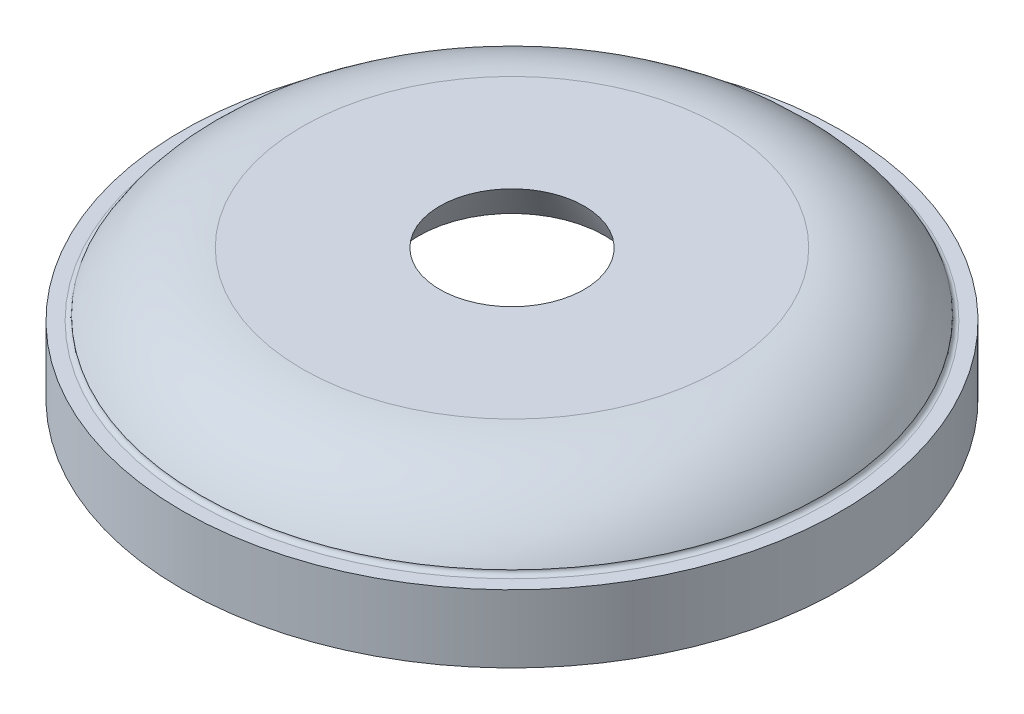
SolidWorks part; units mm, degrees
material "Silica Phenolic"
ref_plane "Piano frontale" through (0, 0, 0) normal (0, 0, 1) x (1, 0, 0)
ref_plane "Piano superiore" through (0, 0, 0) normal (0, 1, 0) x (1, 0, 0)
ref_plane "Piano destro" through (0, 0, 0) normal (1, 0, 0) x (0, 0, -1)
sketch "Schizzo1" plane through (0, 0, 0) normal (0, 0, 1) x (1, 0, 0)
  line L0 (-69, 0) -> (-73, 0)
  line L1 (-73, 0) -> (-73, 15)
  line L4 (-46.4833, 21) -> (-20.6188, 21)
  line L5 (-20.6188, 21) -> (-16, 29)
  line L6 (-16, 29) -> (-46.4833, 29)
  line L7 (0, 0) -> (0, 32.2434) construction
  line L9 (-73, 15) -> (-69, 15)
  line L10 (-69, 15) -> (-69, 16)
  line L11 (-46.4833, 21) -> (-46.4833, 29) construction
  line L13 (69, 16) -> (-69, 16) construction
  line L18 (-69, 4) -> (-69, 0) construction
  line L22 (-69, 4) -> (-69, 0) construction
  line L23 (-69, 0) -> (69, 0) construction
  line L24 (-69, 4) -> (-69, 0)
  arc A3 (-69, 16) -> (-46.4833, 29) centre (-46.4833, 3) cw
  arc A5 (-54.25, 27.8129) -> (-69, 16) centre (-46.4833, 3) ccw construction
  arc A6 (-69, 4) -> (-46.4833, 21) centre (-46.4833, -2.4118) cw
  point P5 (-69, 5.1127)
  dimension "D4" = 30
  dimension "D1" = 8
  dimension "D2" = 4
  dimension "D5" = 146
  dimension "D6" = 32
  dimension "D7" = 29
  dimension "D8" = 15
revolve "Rivoluzione1" add sketch "Schizzo1" angle 360 about L7
fillet "Raccordo1" radius 1 1 edges at (0, 15, -69)
